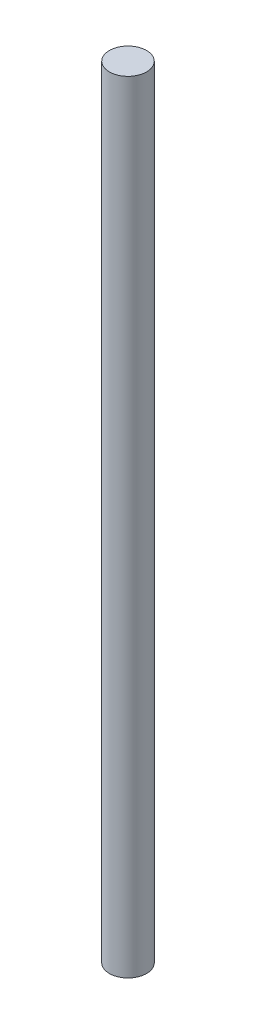
SolidWorks part; units mm, degrees
ref_plane "Front Plane" through (0, 0, 0) normal (0, 0, 1) x (1, 0, 0)
ref_plane "Top Plane" through (0, 0, 0) normal (0, 1, 0) x (1, 0, 0)
ref_plane "Right Plane" through (0, 0, 0) normal (1, 0, 0) x (0, 0, -1)
sketch "Sketch1" plane through (0, 0, 0) normal (0, 1, 0) x (1, 0, 0)
  circle A0 centre (0, 0) radius 5
  dimension "D1" = 10
extrude "Boss-Extrude1" add sketch "Sketch1" along normal blind 210
